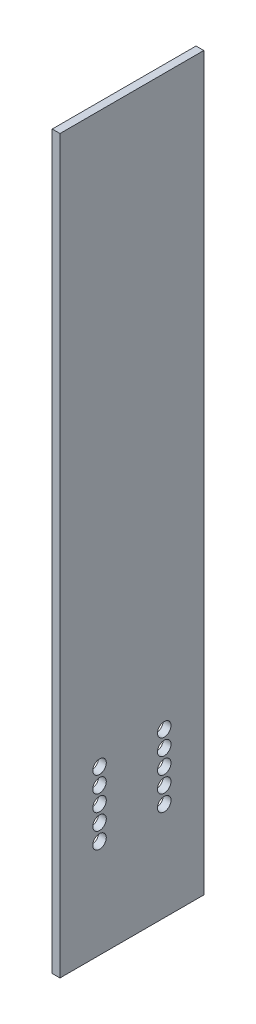
SolidWorks part; units mm, degrees
ref_plane "Front Plane" through (0, 0, 0) normal (0, 0, 1) x (1, 0, 0)
ref_plane "Top Plane" through (0, 0, 0) normal (0, 1, 0) x (1, 0, 0)
ref_plane "Right Plane" through (0, 0, 0) normal (1, 0, 0) x (0, 0, -1)
sketch "Sketch1" plane through (0, 0, 0) normal (1, 0, 0) x (0, 0, -1)
  line L1 (-28.2194, 143.51) -> (28.2194, 143.51)
  line L2 (-28.2194, 143.51) -> (-28.2194, -143.51)
  line L3 (-28.2194, -143.51) -> (28.2194, -143.51)
  line L4 (28.2194, 143.51) -> (28.2194, -143.51)
  line L5 (-28.2194, 143.51) -> (28.2194, -143.51) construction
  line L6 (-28.2194, -143.51) -> (28.2194, 143.51) construction
  point P0 (0, 0)
  dimension "D1" = 56.4388
  dimension "D2" = 287.02
extrude "Boss-Extrude1" add sketch "Sketch1" along normal blind 3.048
sketch "Sketch2" plane through (3.048, 0, 0) normal (1, 0, 0) x (0, 0, -1)
  line L0 (0, 143.51) -> (0, -143.51) construction
  line L1 (28.2194, 143.51) -> (-28.2194, 143.51) construction
  line L2 (-28.2194, -143.51) -> (28.2194, -143.51) construction
  point P0 (-12.7, -98.5012)
  point P9 (12.7, -98.5012)
  dimension "D1" = 12.7
  dimension "D2" = 45.0088
hole_wizard "#4 (0.209) Diameter Hole1" positions "Sketch3" profile "Sketch4" hole size "#4" standard "ANSI Inch" end condition through all
sketch "Sketch3" plane through (3.048, 0, 0) normal (1, 0, 0) x (0, 0, -1)
  point P0 (-12.7, -98.5012)
  point P3 (12.7, -98.5012)
sketch "Sketch4" plane through (3.048, -98.5012, 12.7) normal (0, 1, 0) x (0, 0, -1)
  line L0 (0, 0) -> (0, 3.048)
  line L1 (0, 3.048) -> (2.6543, 3.048)
  line L2 (2.6543, 3.048) -> (2.6543, 0)
  line L5 (2.6543, 0) -> (0, 0)
  line L11 (0, -6.35) -> (0, 107.95) construction
  dimension "Thru Hole Dia." = 5.3086
  dimension "Thru Hole Depth" = 3.048
pattern_linear "LPattern1" count 4 spacing 6.35 along (0, 1, 0) count 2 spacing 6.35 along (0, -1, 0) of "#4 (0.209) Diameter Hole1" pattern seed only yes
equation "\"motor offset\"=6mm"
equation "\"thickness0.25\"=0.225in"
equation "\"thickness0.125\"=0.122in"
equation "\"thickness_acrylic0.1\"= 0.1in"
equation "\"D1@Sketch1\"=\"thickness_acrylic0.1\"+\"thickness0.125\"+2"
equation "\"D2@Sketch2\"=\"thickness0.125\" + 0.5 + 1.15"
